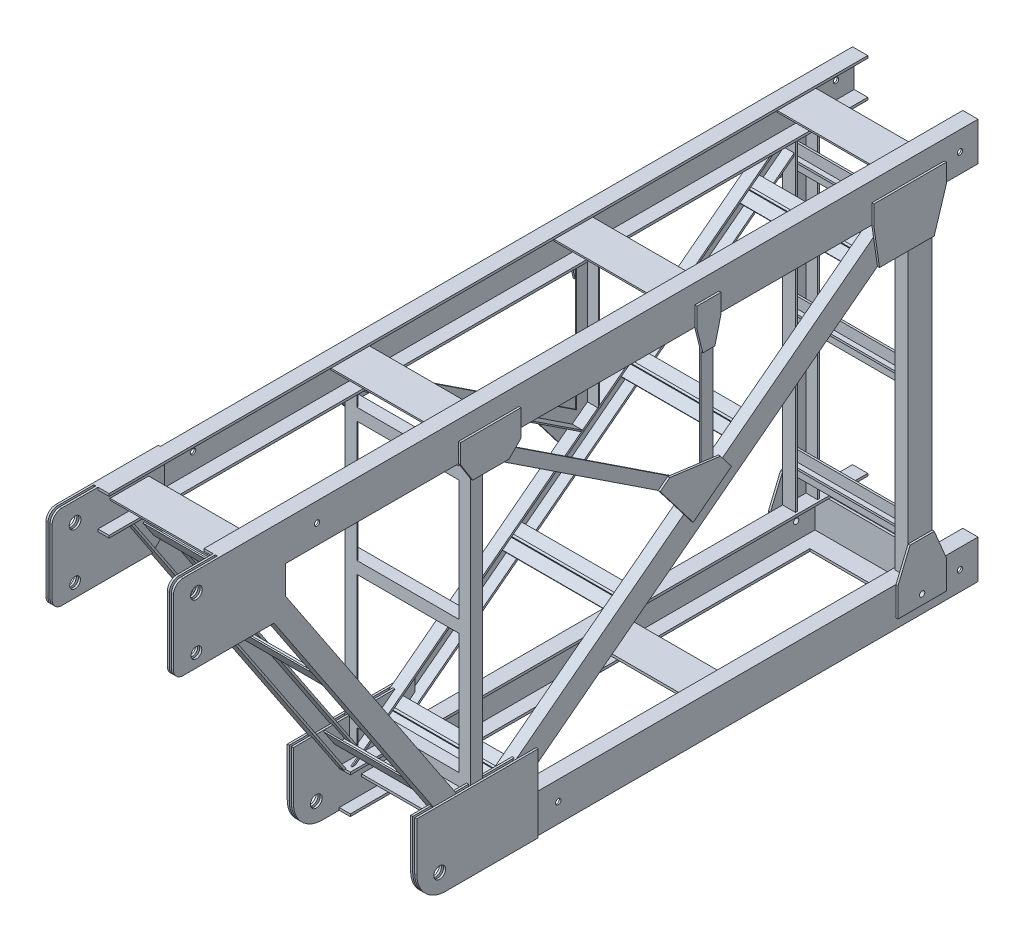
SolidWorks part; units mm, degrees
note: The reader was unsure of these and kept them because the rebuilt part matched: shared geometry of "草图38<2>".
ref_plane "前视基准面" through (0, 0, 0) normal (0, 0, 1) x (1, 0, 0)
ref_plane "上视基准面" through (0, 0, 0) normal (0, 1, 0) x (1, 0, 0)
ref_plane "右视基准面" through (0, 0, 0) normal (1, 0, 0) x (0, 0, -1)
sketch "草图2" plane through (0, 0, 0) normal (0, 0, 1) x (1, 0, 0)
  line L0 (0, 0) -> (0, 160)
  line L1 (0, 160) -> (63, 160)
  line L2 (63, 160) -> (63, 150)
  line L3 (63, 150) -> (6.5, 150)
  line L4 (6.5, 150) -> (6.5, 10)
  line L5 (6.5, 10) -> (63, 10)
  line L6 (63, 10) -> (63, 0)
  line L7 (63, 0) -> (0, 0)
  line L8 (457, 160) -> (520, 160)
  line L9 (520, 160) -> (520, 0)
  line L10 (520, 0) -> (457, 0)
  line L11 (457, 0) -> (457, 10)
  line L12 (457, 10) -> (513.5, 10)
  line L13 (513.5, 10) -> (513.5, 150)
  line L14 (513.5, 150) -> (457, 150)
  line L15 (457, 150) -> (457, 160)
  dimension "D1" = 160
  dimension "D2" = 10
  dimension "D3" = 6.5
  dimension "D4" = 63
  dimension "D5" = 520
extrude "拉伸1" add sketch "草图2" along normal blind 3335
pattern_linear "阵列(线性)2" count 2 spacing 1500 along (0, -1, 0) of "拉伸1"
sketch "草图4" plane through (0, -1340, 0) normal (0, 1, 0) x (1, 0, 0)
  line L0 (0, -3335) -> (0, 0) construction
  line L1 (520, -3335) -> (0, -3335)
  line L2 (520, -3335) -> (520, -2335)
  line L3 (520, -2335) -> (0, -2335)
  line L4 (0, -3335) -> (0, -2335)
  dimension "D1" = 1000
extrude "拉伸2" cut sketch "草图4" against normal blind 1000
sketch "草图5" plane through (0, 0, 0) normal (-1, 0, 0) x (0, 0, 1)
  line L0 (160, 95) -> (320, 95)
  line L1 (320, 95) -> (320, 88.5)
  line L2 (243.25, 88.5) -> (320, 88.5)
  line L3 (243.25, 88.5) -> (243.25, 48.5)
  line L4 (243.25, 48.5) -> (236.75, 48.5)
  line L5 (236.75, 48.5) -> (236.75, 88.5)
  line L6 (236.75, 88.5) -> (160, 88.5)
  line L7 (160, 88.5) -> (160, 95)
  line L8 (0, 160) -> (0, 0) construction
  point P10 (0, 80)
  dimension "D1" = 160
  dimension "D2" = 6.5
  dimension "D3" = 6.5
  dimension "D4" = 40
  dimension "D5" = 160
  dimension "D6" = 15
extrude "拉伸3" add sketch "草图5" against normal blind 520
sketch "草图8" plane through (0, 0, 0) normal (-1, 0, 0) x (0, 0, 1)
  line L0 (240, -1500) -> (240, 160) construction
  line L1 (3335, 160) -> (0, 160) construction
  line L2 (3335, 0) -> (0, 0) construction
  line L3 (190, 0) -> (290, 0)
  line L4 (190, 0) -> (190, -1340)
  line L5 (190, -1340) -> (290, -1340)
  line L6 (290, 0) -> (290, -1340)
  line L7 (2335, -1340) -> (0, -1340) construction
  line L8 (2335, -1500) -> (0, -1500) construction
  line L9 (0, -1340) -> (0, -1500) construction
  dimension "D1" = 50
  dimension "D2" = 50
  dimension "D3" = 240
extrude "拉伸7" add sketch "草图8" against normal blind 520 separate body
sketch "草图10" plane through (0, -1340, 0) normal (0, -1, 0) x (1, 0, 0)
  line L0 (466.7, 290) -> (466.7, 281.5)
  line L1 (520, 290) -> (0, 290) construction
  line L2 (466.7, 281.5) -> (514.7, 281.5)
  line L3 (514.7, 281.5) -> (514.7, 198.5)
  line L4 (514.7, 198.5) -> (466.7, 198.5)
  line L5 (466.7, 198.5) -> (466.7, 190)
  line L6 (520, 190) -> (0, 190) construction
  line L7 (53.3, 190) -> (53.3, 198.5)
  line L8 (53.3, 198.5) -> (5.3, 198.5)
  line L9 (5.3, 198.5) -> (5.3, 281.5)
  line L10 (53.3, 281.5) -> (53.3, 290)
  line L11 (53.3, 290) -> (466.7, 290)
  line L12 (5.3, 281.5) -> (53.3, 281.5)
  line L13 (53.3, 190) -> (466.7, 190)
  line L16 (0, 2335) -> (0, 0) construction
  line L17 (520, 2335) -> (520, 0) construction
  dimension "D1" = 5.3
  dimension "D2" = 5.3
  dimension "D3" = 8.5
  dimension "D4" = 48
extrude "拉伸9" cut sketch "草图10" against normal blind 1340
sketch "草图11" plane through (0, 0, 0) normal (-1, 0, 0) x (0, 0, 1)
  line L0 (3335, 160) -> (3335, 0) construction
  line L1 (3335, 80) -> (0, 80) construction
  line L2 (0, 160) -> (0, 0) construction
  circle A0 centre (3240, 80) radius 11
  dimension "D1" = 22
  dimension "D2" = 95
extrude "拉伸10" cut sketch "草图11" against normal through all
sketch "草图12" plane through (0, 0, 0) normal (-1, 0, 0) x (0, 0, 1)
  line L0 (2145, -1420) -> (290, 0) construction
  line L1 (290, 0) -> (372.2575, 0)
  line L2 (3335, 0) -> (0, 0) construction
  line L3 (372.2575, 0) -> (2122.7505, -1340)
  line L4 (2122.7505, -1340) -> (1958.2354, -1340)
  line L5 (1958.2354, -1340) -> (290, -62.968)
  line L6 (290, -1340) -> (290, 0) construction
  line L7 (290, -62.968) -> (290, 0)
  line L8 (0, -1420) -> (2335, -1420) construction
  line L9 (2335, -1340) -> (0, -1340) construction
  line L10 (0, -1500) -> (0, -1340) construction
  line L11 (2335, -1500) -> (2335, -1340) construction
  dimension "D1" = 50
  dimension "D2" = 50
  dimension "D3" = 190
extrude "拉伸11" add sketch "草图12" against normal blind 48
pattern_linear "阵列(线性)3" count 2 spacing 472 along (1, 0, 0) of "拉伸11"
sketch "草图13" plane through (48, 0, 0) normal (1, 0, 0) x (0, 0, -1)
  line L0 (-358.2737, 0) -> (-290, 0)
  line L1 (-372.2575, 0) -> (-290, 0) construction
  line L2 (-290, 0) -> (-290, -52.2634)
  line L3 (-290, 0) -> (-290, -62.968) construction
  line L4 (-290, -52.2634) -> (-1972.2192, -1340)
  line L5 (-1958.2354, -1340) -> (-2122.7505, -1340) construction
  line L6 (-1972.2192, -1340) -> (-2108.7667, -1340)
  line L7 (-2108.7667, -1340) -> (-358.2737, 0)
  line L8 (-2122.7505, -1340) -> (-372.2575, 0) construction
  line L9 (-290, -62.968) -> (-1958.2354, -1340) construction
  dimension "D1" = 8.5
  dimension "D2" = 8.5
extrude "拉伸12" cut sketch "草图13" against normal blind 42.7
sketch "草图14" plane through (472, 0, 0) normal (-1, 0, 0) x (0, 0, 1)
  line L0 (290, -52.2634) -> (290, 0)
  line L1 (290, 0) -> (290, -62.968) construction
  line L2 (290, 0) -> (358.2737, 0)
  line L3 (372.2575, 0) -> (290, 0) construction
  line L4 (358.2737, 0) -> (2108.7667, -1340)
  line L5 (1958.2354, -1340) -> (2122.7505, -1340) construction
  line L6 (2108.7667, -1340) -> (1972.2192, -1340)
  line L7 (1972.2192, -1340) -> (290, -52.2634)
  line L8 (2122.7505, -1340) -> (372.2575, 0) construction
  line L9 (290, -62.968) -> (1958.2354, -1340) construction
  dimension "D1" = 8.5
  dimension "D2" = 8.5
extrude "拉伸13" cut sketch "草图14" against normal blind 42.7
sketch "草图15" plane through (0, 0, 0) normal (-1, 0, 0) x (0, 0, 1)
  line L0 (3050, 80) -> (2050, -1420) construction
  line L1 (2996.6667, 0) -> (2948.5926, 0)
  line L2 (3335, 0) -> (372.2575, 0) construction
  line L3 (2948.5926, 0) -> (2078.0642, -1305.7927)
  line L4 (2122.7505, -1340) -> (372.2575, 0) construction
  line L5 (2078.0642, -1305.7927) -> (2122.7505, -1340)
  line L6 (2122.7505, -1340) -> (2151.4074, -1340)
  line L7 (2335, -1340) -> (2122.7505, -1340) construction
  line L8 (2151.4074, -1340) -> (3044.7407, 0)
  line L9 (3044.7407, 0) -> (2996.6667, 0)
  line L10 (0, -1420) -> (2335, -1420) construction
  line L11 (3240, 80) -> (0, 80) construction
  line L12 (0, 160) -> (0, 0) construction
  line L13 (2335, -1500) -> (2335, -1340) construction
  line L14 (0, -1340) -> (0, -1500) construction
  dimension "D1" = 40
  dimension "D2" = 40
  dimension "D3" = 285
  dimension "D4" = 190
extrude "拉伸14" add sketch "草图15" against normal blind 43
pattern_linear "阵列(线性)4" count 2 spacing 477 along (1, 0, 0) of "拉伸14"
sketch "草图16" plane through (477, 0, 0) normal (-1, 0, 0) x (0, 0, 1)
  line L0 (2958.2075, 0) -> (3035.1259, 0)
  line L1 (3044.7407, 0) -> (2948.5926, 0) construction
  line L2 (3035.1259, 0) -> (2141.7925, -1340)
  line L3 (2122.7505, -1340) -> (2151.4074, -1340) construction
  line L4 (2141.7925, -1340) -> (2064.8741, -1340)
  line L5 (2064.8741, -1340) -> (2958.2075, 0)
  line L6 (2151.4074, -1340) -> (3044.7407, 0) construction
  line L7 (2948.5926, 0) -> (2078.0642, -1305.7927) construction
  dimension "D1" = 8
  dimension "D2" = 8
extrude "拉伸15" cut sketch "草图16" against normal blind 38
sketch "草图17" plane through (43, 0, 0) normal (1, 0, 0) x (0, 0, -1)
  line L0 (-3035.1259, 0) -> (-2958.2075, 0)
  line L1 (-3044.7407, 0) -> (-2948.5926, 0) construction
  line L2 (-2958.2075, 0) -> (-2064.8741, -1340)
  line L3 (-2122.7505, -1340) -> (-2151.4074, -1340) construction
  line L4 (-2064.8741, -1340) -> (-2141.7925, -1340)
  line L5 (-2141.7925, -1340) -> (-3035.1259, 0)
  line L6 (-2151.4074, -1340) -> (-3044.7407, 0) construction
  line L7 (-2948.5926, 0) -> (-2078.0642, -1305.7927) construction
  dimension "D1" = 8
  dimension "D2" = 8
extrude "拉伸16" cut sketch "草图17" against normal blind 38
sketch "草图18" plane through (0, 0, 0) normal (-1, 0, 0) x (0, 0, 1)
  line L0 (2078.0642, -1305.7927) -> (2078.0642, 0.0067) construction
  line L1 (2078.0642, -1305.7927) -> (372.2575, 0) construction
  line L2 (2948.5926, 0) -> (372.2575, 0) construction
  line L4 (2053.0642, 0) -> (2103.0642, 0)
  line L5 (2053.0642, 0) -> (2053.0642, -1286.6552)
  line L7 (2103.0642, 0) -> (2103.0642, -1268.2927)
  line L8 (2948.5926, 0) -> (2078.0642, -1305.7927) construction
  line L9 (2103.0642, -1268.2927) -> (2078.0642, -1305.7927)
  line L10 (2078.0642, -1305.7927) -> (2053.0642, -1286.6552)
  dimension "D1" = 25
  dimension "D2" = 25
extrude "拉伸17" add sketch "草图18" against normal blind 520 separate body
sketch "草图19" plane through (0, 0, 0) normal (0, 1, 0) x (1, 0, 0)
  line L0 (457, -3335) -> (457, 0) construction
  line L1 (457, -2053.0642) -> (63, -2053.0642)
  line L2 (457, -2053.0642) -> (457, -2103.0642)
  line L3 (457, -2103.0642) -> (63, -2103.0642)
  line L4 (63, -2053.0642) -> (63, -2103.0642)
  line L5 (520, -2053.0642) -> (0, -2053.0642) construction
  line L6 (520, -2103.0642) -> (0, -2103.0642) construction
  line L7 (63, -3335) -> (63, 0) construction
extrude "拉伸18" cut sketch "草图19" against normal through all
sketch "草图20" plane through (457, 0, 0) normal (-1, 0, 0) x (0, 0, 1)
  line L0 (2053.0642, 0) -> (2103.0642, 0)
  line L1 (2103.0642, 0) -> (2103.0642, -1268.2927)
  line L2 (2103.0642, -1268.2927) -> (2078.0642, -1305.7927)
  line L3 (2078.0642, -1305.7927) -> (2053.0642, -1286.6552)
  line L4 (2053.0642, -1286.6552) -> (2078.0642, -1305.7927) construction
  line L5 (2053.0642, -1286.6552) -> (2053.0642, 0) construction
  line L6 (2053.0642, -1286.6552) -> (2053.0642, 0)
extrude "拉伸19" cut sketch "草图20" against normal blind 15
sketch "草图21" plane through (63, 0, 0) normal (1, 0, 0) x (0, 0, -1)
  line L0 (-2103.0642, -1268.2927) -> (-2078.0642, -1305.7927)
  line L1 (-2078.0642, -1305.7927) -> (-2053.0642, -1286.6552)
  line L2 (-2053.0642, -1286.6552) -> (-2053.0642, 0)
  line L3 (-3335, 0) -> (0, 0) construction
  line L4 (-2053.0642, -1286.6552) -> (-2053.0642, 0) construction
  line L5 (-2053.0642, 0) -> (-2103.0642, 0)
  line L6 (-2053.0642, 0) -> (-2103.0642, 0) construction
  line L7 (-2103.0642, 0) -> (-2103.0642, -1268.2927)
extrude "拉伸20" cut sketch "草图21" against normal blind 15
sketch "草图23" plane through (472, 0, 0) normal (-1, 0, 0) x (0, 0, 1)
  line L0 (2098.0642, -1275.7927) -> (2078.0642, -1305.7927)
  line L1 (2078.0642, -1305.7927) -> (2103.0642, -1268.2927) construction
  line L2 (2078.0642, -1305.7927) -> (2053.0642, -1286.6552)
  line L3 (2053.0642, -1286.6552) -> (2053.0642, 0)
  line L4 (2103.0642, 0) -> (2053.0642, 0) construction
  line L5 (2053.0642, 0) -> (2098.0642, 0)
  line L6 (2098.0642, 0) -> (2098.0642, -1275.7927)
  line L8 (2103.0642, -1268.2927) -> (2103.0642, 0) construction
  dimension "D1" = 5
extrude "拉伸21" cut sketch "草图23" against normal blind 45
sketch "草图24" plane through (48, 0, 0) normal (1, 0, 0) x (0, 0, -1)
  line L0 (-2098.0642, -1275.7927) -> (-2078.0642, -1305.7927)
  line L1 (-2103.0642, -1268.2927) -> (-2078.0642, -1305.7927) construction
  line L2 (-2078.0642, -1305.7927) -> (-2053.0642, -1286.6552)
  line L3 (-2053.0642, -1286.6552) -> (-2053.0642, 0)
  line L4 (-2053.0642, 0) -> (-2098.0642, 0)
  line L5 (-2053.0642, 0) -> (-2103.0642, 0) construction
  line L6 (-2098.0642, 0) -> (-2098.0642, -1275.7927)
  line L7 (-2103.0642, 0) -> (-2103.0642, -1268.2927) construction
  dimension "D1" = 5
extrude "拉伸22" cut sketch "草图24" against normal blind 45
pattern_linear "阵列(线性)6" count 4 spacing 925 along (0, 0, 1) of "拉伸3"
sketch "草图27" plane through (0, -1500, 0) normal (0, -1, 0) x (1, 0, 0)
  line L0 (0, 2335) -> (0, 0) construction
  line L1 (0, 240) -> (520, 240)
  line L2 (0, 240) -> (0, 80)
  line L3 (0, 80) -> (520, 80)
  line L4 (520, 240) -> (520, 80)
  line L5 (520, 2335) -> (520, 0) construction
  line L6 (0, 0) -> (63, 0) construction
  line L12 (0, 160) -> (520, 160) construction
  dimension "D1" = 160
  dimension "D2" = 80
extrude "拉伸24" add sketch "草图27" against normal blind 10
sketch "草图28" plane through (0, -1490, 0) normal (0, 1, 0) x (1, 0, 0)
  line L0 (513.5, -2335) -> (513.5, 0) construction
  line L1 (513.5, -162.5) -> (6.5, -162.5)
  line L2 (513.5, -162.5) -> (513.5, -152.5)
  line L3 (513.5, -152.5) -> (6.5, -152.5)
  line L4 (6.5, -162.5) -> (6.5, -152.5)
  line L5 (6.5, -2335) -> (6.5, 0) construction
  line L6 (63, -240) -> (63, -80) construction
  line L7 (457, -240) -> (457, -80) construction
  line L8 (63, -80) -> (457, -80) construction
  line L9 (457, -160) -> (63, -160) construction
  dimension "D1" = 10
  dimension "D2" = 5
extrude "拉伸25" add sketch "草图28" along normal blind 140
sketch "草图29" plane through (0, 0, 0) normal (-1, 0, 0) x (0, 0, 1)
  line L0 (240, -1340) -> (190, -1340) construction
  line L1 (240, -1340) -> (240, 160) construction
  line L2 (3335, 160) -> (0, 160) construction
  line L3 (231.5, -1160) -> (231.5, -1260)
  line L4 (231.5, -1260) -> (240, -1260)
  line L5 (240, -1260) -> (240, -1214.25)
  line L6 (240, -1214.25) -> (260, -1214.25)
  line L7 (260, -1214.25) -> (260, -1205.75)
  line L8 (260, -1205.75) -> (240, -1205.75)
  line L9 (240, -1205.75) -> (240, -1160)
  line L10 (240, -1160) -> (231.5, -1160)
  line L11 (190, 0) -> (190, -1340) construction
  line L12 (240, -1340) -> (290, -1340) construction
  dimension "D1" = 100
  dimension "D2" = 8.5
  dimension "D3" = 8.5
  dimension "D4" = 20
  dimension "D5" = 80
extrude "拉伸26" add sketch "草图29" against normal blind 520
pattern_linear "阵列(线性)9" count 3 spacing 550 along (0, 1, 0) of "拉伸26"
sketch "草图30" plane through (0, 0, 0) normal (-1, 0, 0) x (0, 0, 1)
  line L0 (2249.507, -1500) -> (80.9859, 160) construction
  line L1 (2335, -1500) -> (0, -1500) construction
  line L2 (3335, 160) -> (0, 160) construction
  line L3 (290, -62.968) -> (1958.2354, -1340) construction
  line L5 (290, -62.968) -> (320.3924, -23.2653) construction
  line L6 (320.3924, -23.2653) -> (350.7847, 16.4374) construction
  line L7 (2078.0642, -1305.7927) -> (372.2575, 0) construction
  line L8 (400.2228, -95.0799) -> (479.6282, -155.8647)
  line L9 (479.6282, -155.8647) -> (484.7949, -149.1152)
  line L10 (484.7949, -149.1152) -> (448.4669, -121.3062)
  line L11 (448.4669, -121.3062) -> (460.6238, -105.4251)
  line L12 (460.6238, -105.4251) -> (453.8744, -100.2584)
  line L13 (453.8744, -100.2584) -> (441.7174, -116.1395)
  line L14 (441.7174, -116.1395) -> (405.3895, -88.3305)
  line L15 (405.3895, -88.3305) -> (400.2228, -95.0799)
  dimension "D1" = 100
  dimension "D2" = 8.5
  dimension "D3" = 8.5
  dimension "D4" = 20
  dimension "D5" = 80
extrude "拉伸27" add sketch "草图30" against normal blind 520
pattern_linear "阵列(线性)10" count 4 spacing 620 along (0, -0.6078, 0.7941) of "拉伸27"
sketch "草图31" plane through (520, 0, 0) normal (1, 0, 0) x (0, 0, -1)
  line L0 (-2953.9085, -59.6303) -> (-2909.5325, -126.1943)
  line L1 (-2953.9085, -59.6303) -> (-2958.0688, -62.4038)
  line L2 (-2909.5325, -126.1943) -> (-2913.6928, -128.9678)
  line L3 (-2958.0688, -62.4038) -> (-2913.6928, -128.9678)
  line L4 (-2151.4074, -1340) -> (-2118.1253, -1317.812) construction
  line L5 (-2118.1253, -1317.812) -> (-2084.8433, -1295.624) construction
  line L6 (-3103.3333, 160) -> (-2118.1253, -1317.812) construction
  line L7 (-3335, 160) -> (0, 160) construction
  line L8 (-2151.4074, -1340) -> (-3044.7407, 0) construction
  line L10 (-2948.5926, 0) -> (-2078.0642, -1305.7927) construction
  line L11 (-2958.0688, -62.4038) -> (-2933.8006, -94.299) construction
  line L12 (-2953.9085, -59.6303) -> (-2913.6928, -128.9678) construction
  line L13 (-2933.8006, -94.299) -> (-2909.5325, -126.1943) construction
  dimension "D1" = 80
  dimension "D2" = 5
  dimension "D3" = 100
extrude "拉伸28" add sketch "草图31" against normal blind 520
sketch "草图32" plane through (0, -1381.6902, 2072.5353) normal (0, 0.5547, -0.8321) x (-1, 0, 0)
  line L1 (-457, 1551.4183) -> (-63, 1551.4183)
  line L2 (-457, 1551.4183) -> (-457, 1546.4183)
  line L3 (-457, 1546.4183) -> (-63, 1546.4183)
  line L4 (-63, 1551.4183) -> (-63, 1546.4183)
  line L5 (-63, 1983.0532) -> (-63, 133.128) construction
  line L6 (-457, 1983.0532) -> (-457, 133.128) construction
  line L7 (-260, 1508.9183) -> (-260, 1548.9183) construction
  line L8 (-5, 1508.9183) -> (-515, 1508.9183) construction
  line L9 (-5, 1548.9183) -> (-515, 1548.9183) construction
  line L11 (-515, 1508.9183) -> (-515, 1588.9183) construction
  line L12 (-260, 1548.9183) -> (-260, 1588.9183) construction
  line L13 (-5, 1588.9183) -> (-515, 1588.9183) construction
  dimension "D1" = 2.5
  dimension "D2" = 2.5
extrude "拉伸29" add sketch "草图32" along normal blind 15
pattern_linear "阵列(线性)11" count 3 spacing 675 along (0, -0.8321, -0.5547) of "拉伸28", "拉伸29"
sketch "草图38" plane through (0, 0, 2103.0642) normal (0, 0, 1) x (1, 0, 0)
  line L0 (0, -1268.2927) -> (0, 0) construction
  line L1 (0, -1158.2927) -> (520, -1158.2927)
  line L2 (0, -1158.2927) -> (0, -1208.2927)
  line L3 (0, -1208.2927) -> (520, -1208.2927)
  line L4 (520, -1158.2927) -> (520, -1208.2927)
  line L5 (520, -1268.2927) -> (520, 0) construction
  dimension "D1" = 50
  dimension "D2" = 60
extrude "拉伸36" add sketch "草图38" against normal blind 50
extrude "拉伸37" add sketch "草图38<2>" against normal blind 50
sketch "草图38<2>" plane through (0, 0, 2103.0642) normal (0, 0, 1) x (1, 0, 0) same geometry as "草图38"
pattern_linear "阵列(线性)13" count 3 spacing 550 along (0, 1, 0) of "拉伸37"
sketch "草图39" plane through (0, 0, 2053.0642) normal (0, 0, -1) x (-1, 0, 0)
  line L0 (-3, -1286.6552) -> (-3, -1208.2927) construction
  line L1 (-517, -1208.2927) -> (-3, -1208.2927)
  line L2 (-517, -1208.2927) -> (-517, -1163.2927)
  line L3 (-517, -1163.2927) -> (-3, -1163.2927)
  line L4 (-3, -1208.2927) -> (-3, -1163.2927)
  line L6 (-517, -658.2927) -> (-3, -658.2927)
  line L7 (-517, -658.2927) -> (-517, -613.2927)
  line L8 (-517, -613.2927) -> (-3, -613.2927)
  line L9 (-3, -658.2927) -> (-3, -613.2927)
  line L10 (-517, -108.2927) -> (-3, -108.2927)
  line L11 (-517, -108.2927) -> (-517, -63.2927)
  line L12 (-517, -63.2927) -> (-3, -63.2927)
  line L13 (-3, -108.2927) -> (-3, -63.2927)
  dimension "D1" = 45
extrude "拉伸38" cut sketch "草图39" against normal blind 45
sketch "草图40" plane through (520, 0, 0) normal (1, 0, 0) x (0, 0, -1)
  line L1 (-2335, -1500) -> (-1831.4789, -1500)
  line L2 (-2335, -1500) -> (-2335, -1180)
  line L3 (-2335, -1180) -> (-1831.4789, -1180)
  line L4 (-1831.4789, -1500) -> (-1831.4789, -1180)
  line L6 (-1831.4789, -1180) -> (-1801.0865, -1219.7027) construction
  line L7 (-290, -62.968) -> (-1958.2354, -1340) construction
  line L8 (-1831.4789, -1180) -> (-1861.8712, -1140.2973) construction
  line L9 (-2053.0642, -1286.6552) -> (-372.2575, 0) construction
  dimension "D1" = 320
extrude "拉伸39" add sketch "草图40" along normal blind 8.5
pattern_linear "阵列(线性)15" count 2 spacing 17 along (-1, 0, 0) of "拉伸39"
pattern_linear "阵列(线性)16" count 2 spacing 511.5 along (-1, 0, 0) of "拉伸39", "阵列(线性)15"
sketch "草图41" plane through (0, 0, 2335) normal (0, 0, 1) x (1, 0, 0)
  line L0 (63, -1500) -> (-8.5, -1500) construction
  line L1 (8.5, -1500) -> (0, -1500)
  line L2 (8.5, -1500) -> (8.5, -1340)
  line L3 (8.5, -1340) -> (0, -1340)
  line L4 (0, -1500) -> (0, -1340)
  line L5 (8.5, -1340) -> (0, -1340) construction
  line L6 (8.5, -1350) -> (8.5, -1490) construction
  line L7 (528.5, -1500) -> (457, -1500) construction
  line L8 (17, -1340) -> (503, -1340)
  line L9 (17, -1340) -> (17, -1500)
  line L10 (17, -1500) -> (503, -1500)
  line L11 (503, -1340) -> (503, -1500)
  line L12 (503, -1350) -> (503, -1490) construction
  line L13 (520, -1340) -> (511.5, -1340) construction
  line L14 (511.5, -1340) -> (520, -1340)
  line L15 (511.5, -1340) -> (511.5, -1500)
  line L16 (511.5, -1500) -> (520, -1500)
  line L17 (520, -1340) -> (520, -1500)
  line L18 (511.5, -1350) -> (511.5, -1490) construction
  line L19 (63, -1340) -> (17, -1340) construction
  line L20 (17, -1350) -> (17, -1490) construction
  dimension "D1" = 8.5
extrude "拉伸40" cut sketch "草图41" against normal blind 190
sketch "草图42" plane through (503, 0, 0) normal (-1, 0, 0) x (0, 0, 1)
  line L0 (1831.4789, -1420) -> (1335, -1420) construction
  line L1 (1893.0642, -1415) -> (2053.0642, -1415)
  line L2 (1893.0642, -1415) -> (1893.0642, -1425)
  line L3 (1893.0642, -1425) -> (2053.0642, -1425)
  line L4 (2053.0642, -1415) -> (2053.0642, -1425)
  line L5 (1831.4789, -1490) -> (1831.4789, -1350) construction
  line L8 (2053.0642, 0) -> (2053.0642, -1180) construction
  dimension "D1" = 10
  dimension "D2" = 160
  dimension "D3" = 5
extrude "拉伸41" add sketch "草图42" along normal blind 501.5
fillet "圆角1" radius 120 4 edges at (524.25, -1500, 2335) (-4.25, -1500, 2335) (12.75, -1500, 2335) (507.25, -1500, 2335)
sketch "草图43" plane through (-8.5, 0, 0) normal (-1, 0, 0) x (0, 0, 1)
  line L0 (2215, -1500) -> (1831.4789, -1500) construction
  line L1 (2335, -1180) -> (2335, -1380) construction
  circle A0 centre (2240, -1420) radius 24.25
  dimension "D1" = 48.5
  dimension "D2" = 80
  dimension "D3" = 95
extrude "拉伸42" cut sketch "草图43" against normal through all
sketch "草图44" plane through (0, 0, 0) normal (-1, 0, 0) x (0, 0, 1)
  line L1 (3335, 160) -> (2870, 160)
  line L2 (3335, 160) -> (3335, -190)
  line L3 (3335, -190) -> (2870, -190)
  line L4 (2870, 160) -> (2870, -190)
  line L5 (2948.5926, 0) -> (3015.1567, -44.376) construction
  line L6 (2258.074, -1180) -> (3044.7407, 0) construction
  line L7 (2870, -190) -> (2981.8747, -22.188) construction
  dimension "D1" = 350
extrude "拉伸43" add sketch "草图44" along normal blind 8.5
pattern_linear "阵列(线性)17" count 2 spacing 17 along (1, 0, 0) of "拉伸43"
sketch "草图45" plane through (0, 0, 3335) normal (0, 0, 1) x (1, 0, 0)
  line L0 (63, 160) -> (-8.5, 160) construction
  line L1 (0, -190) -> (8.5, -190)
  line L2 (0, -190) -> (0, 160)
  line L3 (0, 160) -> (8.5, 160)
  line L4 (8.5, -190) -> (8.5, 160)
  line L5 (8.5, -190) -> (8.5, 0) construction
  line L6 (520, 160) -> (457, 160) construction
  line L7 (17, -190) -> (513.5, -190)
  line L8 (17, -190) -> (17, 160)
  line L9 (17, 160) -> (513.5, 160)
  line L10 (513.5, -190) -> (513.5, 160)
  line L11 (513.5, 150) -> (513.5, 10) construction
extrude "拉伸44" cut sketch "草图45" against normal blind 190
chamfer "倒角1" distance 50 angle 45 2 edges at (-4.25, -190, 2870) (12.75, -190, 2870)
sketch "草图46" plane through (-8.5, 0, 0) normal (-1, 0, 0) x (0, 0, 1)
  line L0 (3335, 160) -> (2870, 160) construction
  line L2 (3335, -190) -> (3335, 160) construction
  circle A0 centre (3240, 80) radius 24.25
  dimension "D1" = 48.5
  dimension "D2" = 80
  dimension "D3" = 95
extrude "拉伸45" cut sketch "草图46" against normal through all
sketch "草图47" plane through (0, 0, 0) normal (-1, 0, 0) x (0, 0, 1)
  line L0 (140, 80) -> (140, 0)
  line L1 (190, 0) -> (0, 0) construction
  line L2 (140, 0) -> (190, -160)
  line L3 (190, -160) -> (416.7566, -160)
  line L5 (416.7566, -160) -> (440, 0)
  line L6 (2053.0642, 0) -> (372.2575, 0) construction
  line L7 (440, 0) -> (440, 80)
  line L8 (440, 80) -> (140, 80)
  line L9 (190, 0) -> (190, -1340) construction
  line L10 (190, 0) -> (190, -1340) construction
  line L11 (0, 80) -> (2870, 80) construction
  line L12 (0, 160) -> (0, 0) construction
  line L13 (2870, 160) -> (2870, 0) construction
  line L14 (190, 0) -> (190, -160) construction
  line L15 (290, -62.968) -> (1831.4789, -1242.968) construction
  line L17 (1831.4789, -1500) -> (0, -1500) construction
  line L21 (140, -1460) -> (340, -1460)
  line L22 (340, -1460) -> (340, -1340)
  line L24 (1831.4789, -1340) -> (290, -1340) construction
  line L26 (340, -1340) -> (290, -1220)
  line L27 (290, -1340) -> (290, -62.968) construction
  line L29 (290, -1220) -> (190, -1220)
  line L30 (190, -1220) -> (140, -1340)
  line L31 (190, -1340) -> (0, -1340) construction
  line L32 (140, -1340) -> (140, -1460)
  line L33 (2053.0642, 0) -> (2103.0642, 0) construction
  line L34 (2103.0642, 0) -> (2103.0642, -1180) construction
  line L35 (2078.0642, 0) -> (2078.0642, -1180) construction
  line L36 (2053.0642, -1180) -> (2103.0642, -1180) construction
  line L37 (1903.0642, 80) -> (2153.0642, 80)
  line L38 (2153.0642, 80) -> (2153.0642, 0)
  line L39 (2870, 0) -> (2103.0642, 0) construction
  line L40 (2153.0642, 0) -> (2103.0642, -80)
  line L41 (2103.0642, -80) -> (1903.0642, -80)
  line L44 (1903.0642, -80) -> (1903.0642, 80)
  dimension "D1" = 300
  dimension "D2" = 50
  dimension "D3" = 120
  dimension "D4" = 200
  dimension "D5" = 40
  dimension "D6" = 75
  dimension "D7" = 80
  dimension "D8" = 250
extrude "拉伸46" add sketch "草图47" along normal blind 8.5
pattern_linear "阵列(线性)19" count 2 spacing 528.5 along (1, 0, 0) of "拉伸46"
pattern_linear "阵列(线性)20" count 2 spacing 950 along (0, 0, -1) of "拉伸41"
sketch "草图50" plane through (0, 0, 0) normal (-1, 0, 0) x (0, 0, 1)
  line L0 (1124.1177, -701.484) -> (1124.1177, 0) construction
  line L1 (416.7566, -160) -> (1831.4789, -1242.968) construction
  line L2 (1903.0642, 0) -> (440, 0) construction
  line L3 (1099.1177, 0) -> (1149.1177, 0)
  line L4 (1149.1177, 0) -> (1149.1177, -594.6854)
  line L5 (1913.7364, -1180) -> (433.2206, -46.6672) construction
  line L6 (1149.1177, -594.6854) -> (1099.1177, -556.4105)
  line L7 (1099.1177, -556.4105) -> (1099.1177, 0)
  dimension "D1" = 25
  dimension "D2" = 25
extrude "拉伸48" add sketch "草图50" against normal blind 50
sketch "草图53" plane through (0, 0, 0) normal (-1, 0, 0) x (0, 0, 1)
  line L0 (1149.1177, -566.5851) -> (2007.6756, 0)
  line L1 (1903.0642, 0) -> (1149.1177, 0) construction
  line L2 (2007.6756, 0) -> (2053.0642, 0)
  line L3 (2870, 0) -> (2153.0642, 0) construction
  line L4 (2098.4527, 0) -> (1171.431, -611.7662)
  line L5 (1913.7364, -1180) -> (1149.1177, -594.6854) construction
  line L6 (1149.1177, -594.6854) -> (1149.1177, 0) construction
  line L7 (1149.1177, -566.5851) -> (1149.1177, -594.6854)
  line L8 (1149.1177, -594.6854) -> (1171.431, -611.7662)
  line L9 (2053.0642, 0) -> (2098.4527, 0)
  line L10 (2053.0642, -80) -> (2053.0642, -1180) construction
  dimension "D2" = 50
extrude "拉伸55" add sketch "草图53" against normal blind 50
pattern_linear "阵列(线性)21" count 2 spacing 470 along (1, 0, 0) of "拉伸48", "拉伸55"
sketch "草图54" plane through (470, 0, 0) normal (-1, 0, 0) x (0, 0, 1)
  line L0 (1149.1177, 0) -> (1104.1177, 0)
  line L1 (1149.1177, 0) -> (1099.1177, 0) construction
  line L2 (1104.1177, 0) -> (1104.1177, -560.238)
  line L3 (1099.1177, -556.4105) -> (1171.431, -611.7662) construction
  line L4 (1104.1177, -560.238) -> (1167.2283, -608.549)
  line L5 (1167.2283, -608.549) -> (2089.375, 0)
  line L6 (2098.4527, 0) -> (2007.6756, 0) construction
  line L7 (2089.375, 0) -> (2007.6756, 0)
  line L8 (2007.6756, 0) -> (1149.1177, -566.5851)
  line L9 (1149.1177, -566.5851) -> (1149.1177, 0)
  line L10 (1099.1177, 0) -> (1099.1177, -556.4105) construction
  line L11 (1171.431, -611.7662) -> (2098.4527, 0) construction
  dimension "D1" = 5
  dimension "D2" = 5
extrude "拉伸56" cut sketch "草图54" against normal blind 45
sketch "草图55" plane through (50, 0, 0) normal (1, 0, 0) x (0, 0, -1)
  line L0 (-1104.1177, 0) -> (-1149.1177, 0)
  line L1 (-1149.1177, 0) -> (-1099.1177, 0) construction
  line L2 (-1149.1177, 0) -> (-1149.1177, -566.5851)
  line L3 (-1149.1177, -566.5851) -> (-2007.6756, 0)
  line L4 (-2007.6756, 0) -> (-2089.375, 0)
  line L5 (-2098.4527, 0) -> (-2007.6756, 0) construction
  line L6 (-2089.375, 0) -> (-1167.2283, -608.549)
  line L7 (-1099.1177, -556.4105) -> (-1171.431, -611.7662) construction
  line L8 (-1167.2283, -608.549) -> (-1104.1177, -560.238)
  line L9 (-1104.1177, -560.238) -> (-1104.1177, 0)
  line L10 (-1099.1177, 0) -> (-1099.1177, -556.4105) construction
  line L11 (-1171.431, -611.7662) -> (-2098.4527, 0) construction
  dimension "D1" = 5
  dimension "D2" = 5
extrude "拉伸57" cut sketch "草图55" against normal blind 45
chamfer "倒角2" distance 50 angle 45 2 edges at (524.25, -80, 1903.0642) (-4.25, -80, 1903.0642)
sketch "草图56" plane through (0, 0, 0) normal (-1, 0, 0) x (0, 0, 1)
  line L0 (1124.1177, 160) -> (1124.1177, -701.484) construction
  line L1 (2870, 160) -> (0, 160) construction
  line L2 (416.7566, -160) -> (1831.4789, -1242.968) construction
  line L3 (1099.1177, 0) -> (1124.1177, 0) construction
  line L4 (1099.1177, 0) -> (1099.1177, -556.4105) construction
  line L5 (1124.1177, 0) -> (1149.1177, 0) construction
  line L6 (1074.1177, 80) -> (1174.1177, 80)
  line L7 (1174.1177, 80) -> (1174.1177, 0)
  line L8 (1903.0642, 0) -> (1149.1177, 0) construction
  line L9 (1174.1177, 0) -> (1149.1177, -100)
  line L10 (1149.1177, -566.5851) -> (1149.1177, 0) construction
  line L11 (1149.1177, -100) -> (1099.1177, -100)
  line L12 (1099.1177, -100) -> (1074.1177, 0)
  line L13 (1099.1177, 0) -> (440, 0) construction
  line L14 (1074.1177, 0) -> (1074.1177, 80)
  line L15 (1149.1177, -566.5851) -> (1074.77, -663.7084) construction
  line L16 (1030.4667, -566.8262) -> (1189.2775, -688.3957)
  line L17 (1030.4667, -566.8262) -> (1167.2323, -388.1641)
  line L18 (1189.2775, -688.3957) -> (1326.0431, -509.7336)
  line L19 (1167.2323, -388.1641) -> (1326.0431, -509.7336)
  line L20 (1171.431, -611.7662) -> (1977.2271, -80) construction
  dimension "D1" = 80
  dimension "D2" = 100
  dimension "D3" = 100
  dimension "D4" = 200
  dimension "D5" = 50
  dimension "D6" = 225
extrude "拉伸58" add sketch "草图56" along normal blind 8.5
pattern_linear "阵列(线性)22" count 2 spacing 528.5 along (1, 0, 0) of "拉伸58"
chamfer "倒角3" distance 150 angle 45 2 edges at (524.25, -388.1641, 1167.2323) (-4.25, -388.1641, 1167.2323)
pattern_linear "阵列(线性)23" count 2 spacing 520 along (1, 0, 0) of "拉伸43"
pattern_linear "阵列(线性)24" count 2 spacing 503 along (1, 0, 0) of "拉伸43"
sketch "草图57" plane through (520, 0, 0) normal (1, 0, 0) x (0, 0, -1)
  line L0 (-3335, 160) -> (0, 160) construction
  line L1 (-3335, -190) -> (-3335, 160) construction
  circle A0 centre (-3240, 80) radius 24.25
  circle A1 centre (-3240, -135) radius 22.25
  dimension "D1" = 48.5
  dimension "D2" = 44.5
  dimension "D3" = 80
  dimension "D4" = 95
  dimension "D5" = 95
  dimension "D6" = 215
extrude "拉伸59" cut sketch "草图57" against normal through all
fillet "圆角2" radius 40 8 edges at (-4.25, -190, 3335) (12.75, -190, 3335) (-4.25, 160, 3335) (12.75, 160, 3335) (515.75, 160, 3335) (515.75, -190, 3335) (498.75, 160, 3335) (498.75, -190, 3335)
sketch "草图58" plane through (528.5, 0, 0) normal (1, 0, 0) x (0, 0, -1)
  line L0 (-2240, -1420) -> (0, -1420) construction
  line L1 (0, -1500) -> (0, -1340) construction
  line L2 (-3240, 80) -> (0, 80) construction
  line L3 (0, 0) -> (0, 160) construction
  circle A0 centre (-2740, 80) radius 11
  circle A1 centre (-1740, -1420) radius 11
  circle A2 centre (-240, -1420) radius 11
  circle A3 centre (-75, -1420) radius 11
  circle A4 centre (-75, 80) radius 11
  dimension "D1" = 22
  dimension "D5" = 22
  dimension "D2" = 500
  dimension "D3" = 1500
  dimension "D4" = 500
  dimension "D6" = 75
  dimension "D7" = 75
extrude "拉伸60" cut sketch "草图58" against normal through all
